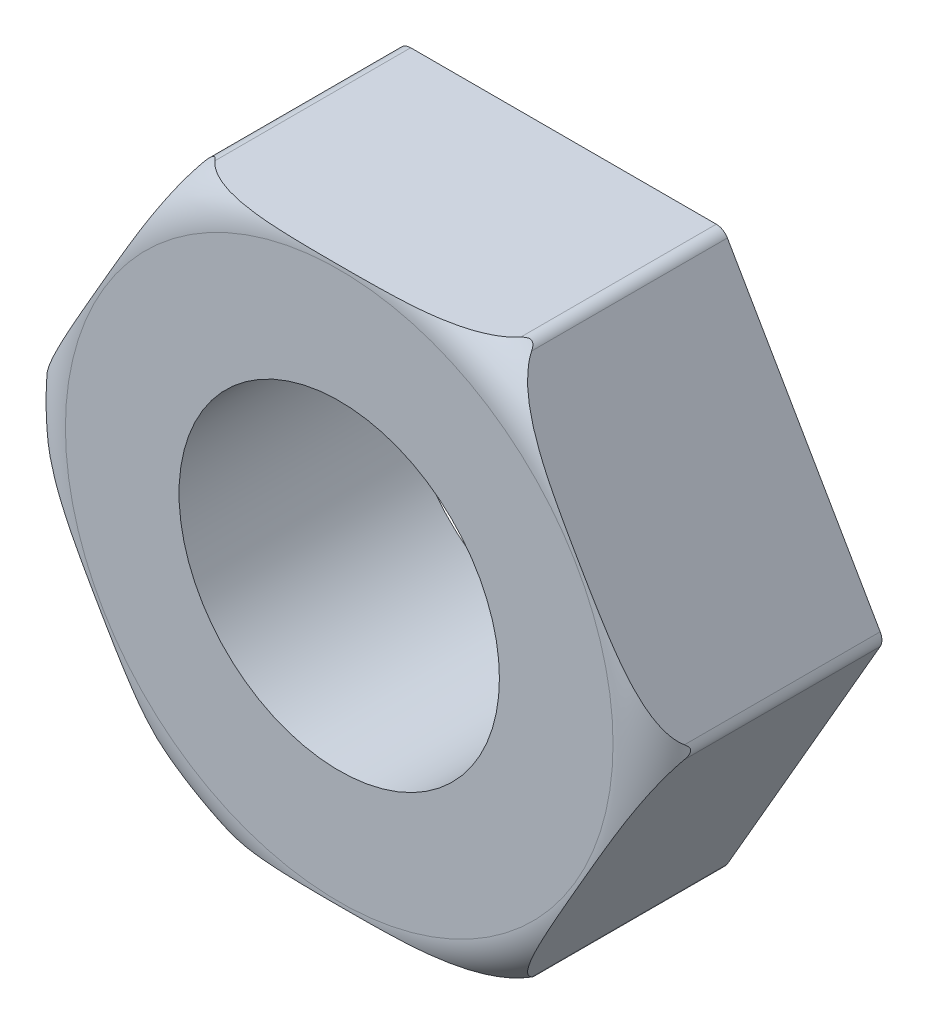
SolidWorks part; units mm, degrees
ref_plane "Front" through (0, 0, 0) normal (0, 0, 1) x (1, 0, 0)
ref_plane "Top" through (0, 0, 0) normal (0, 1, 0) x (1, 0, 0)
ref_plane "Right" through (0, 0, 0) normal (1, 0, 0) x (0, 0, -1)
sketch "Sketch1" plane through (0, 0, 0) normal (0, 0, 1) x (1, 0, 0)
  line L1 (3.175, 5.4993) -> (-3.175, 5.4993)
  line L2 (-3.175, 5.4993) -> (-6.35, 0)
  line L3 (-6.35, 0) -> (-3.175, -5.4993)
  line L4 (-3.175, -5.4993) -> (3.175, -5.4993)
  line L5 (3.175, -5.4993) -> (6.35, 0)
  line L6 (6.35, 0) -> (3.175, 5.4993)
  circle A0 centre (0, 0) radius 5.4993 construction
  circle A1 centre (0, 0) radius 3.175
  dimension "D2" = 6.35
  dimension "D1" = 6.35
extrude "Extrude1" add sketch "Sketch1" along normal mid plane 4.445
sketch "Sketch7" plane through (0, 0, 0) normal (0, 1, 0) x (1, 0, 0)
  line L0 (0, 4.4138) -> (0, -3.6713) construction
  line L1 (5.311, -2.2225) -> (5.4272, -2.2225)
  line L2 (6.35, -1.2997) -> (6.7107, -1.9321)
  line L3 (5.311, -2.2225) -> (5.311, -2.7305)
  line L4 (5.311, -2.7305) -> (5.4272, -2.7305)
  line L9 (6.35, -2.2225) -> (3.175, -2.2225) construction
  line L10 (6.35, -2.2225) -> (6.35, 2.2225) construction
  arc A0 (5.4272, -2.7305) -> (6.7107, -1.9321) centre (5.4272, -1.2997) ccw
  arc A1 (5.4272, -2.2225) -> (6.35, -1.2997) centre (5.4272, -1.2997) ccw
  dimension "D1" = 0.508
revolve "Cut-Revolve2" cut sketch "Sketch7" angle 360 about L0
fillet "Fillet2" radius 0.254 6 edges at (-3.175, 5.4993, -0.4614) (3.175, 5.4993, -0.4614) (6.35, 0, -0.4614) (3.175, -5.4993, -0.4614) (-3.175, -5.4993, -0.4614) (-6.35, 0, -0.4614)
ref_plane "Plane1" through (0, 0, -3.4925) normal (0, 0, 1) x (1, 0, 0)
